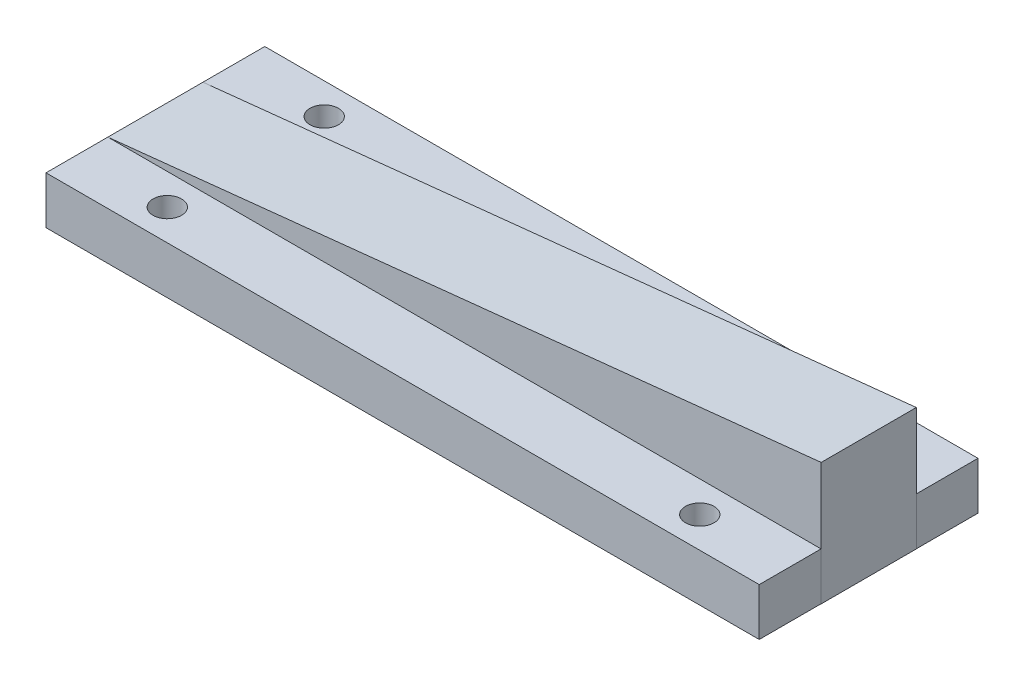
SolidWorks part; units mm, degrees
ref_plane "Front Plane" through (0, 0, 0) normal (0, 0, 1) x (1, 0, 0)
ref_plane "Top Plane" through (0, 0, 0) normal (0, 1, 0) x (1, 0, 0)
ref_plane "Right Plane" through (0, 0, 0) normal (1, 0, 0) x (0, 0, -1)
sketch "Sketch1" plane through (0, 0, 0) normal (0, 1, 0) x (1, 0, 0)
  line L1 (-75, -10) -> (75, -10)
  line L2 (-75, -10) -> (-75, 10)
  line L3 (-75, 10) -> (75, 10)
  line L4 (75, -10) -> (75, 10)
  line L5 (-75, -10) -> (75, 10) construction
  line L6 (-75, 10) -> (75, -10) construction
  point P0 (0, 0)
  dimension "D1" = 20
  dimension "D2" = 150
extrude "Boss-Extrude1" add sketch "Sketch1" along normal blind 10
sketch "Sketch2" plane through (0, 0, 0) normal (0, 0, 1) x (1, 0, 0)
  line L0 (-75, 10) -> (75, 10)
  line L1 (75, 10) -> (75, 25.7656)
  line L2 (75, 25.7656) -> (-75, 10)
  dimension "D1" = 6
extrude "Boss-Extrude2" add sketch "Sketch2" along normal mid plane 20
sketch "Sketch3" plane through (0, 0, 0) normal (0, 0, -1) x (-1, 0, 0)
  line L0 (75, 10) -> (75, 0)
  line L1 (75, 10) -> (-74.9705, 10)
  line L2 (75, 0) -> (-74.9705, 0)
  line L3 (-74.9705, 10) -> (-74.9705, 0)
extrude "Boss-Extrude3" add sketch "Sketch3" along normal mid plane 46
sketch "Sketch4" plane through (0, 10, 0) normal (0, 1, 0) x (1, 0, 0)
  line L0 (-75, -10) -> (-75, -23) construction
  line L1 (-75, 23) -> (-75, 10) construction
  line L2 (74.9705, 23) -> (74.9705, 10) construction
  line L3 (74.9705, -10) -> (74.9705, -23) construction
  line L4 (-75, -23) -> (74.9705, -23) construction
  line L5 (-75, 23) -> (74.9705, 23) construction
  circle A0 centre (-56, 16.5) radius 3
  circle A1 centre (55.9705, 16.5) radius 3
  circle A2 centre (55.9705, -16.5) radius 3
  circle A3 centre (-56, -16.5) radius 3
  dimension "D1" = 6
  dimension "D2" = 19
  dimension "D3" = 19
  dimension "D4" = 19
  dimension "D5" = 19
  dimension "D6" = 6.5
  dimension "D7" = 6.5
  dimension "D8" = 6.5
  dimension "D9" = 6.5
extrude "Cut-Extrude1" cut sketch "Sketch4" against normal blind 46
